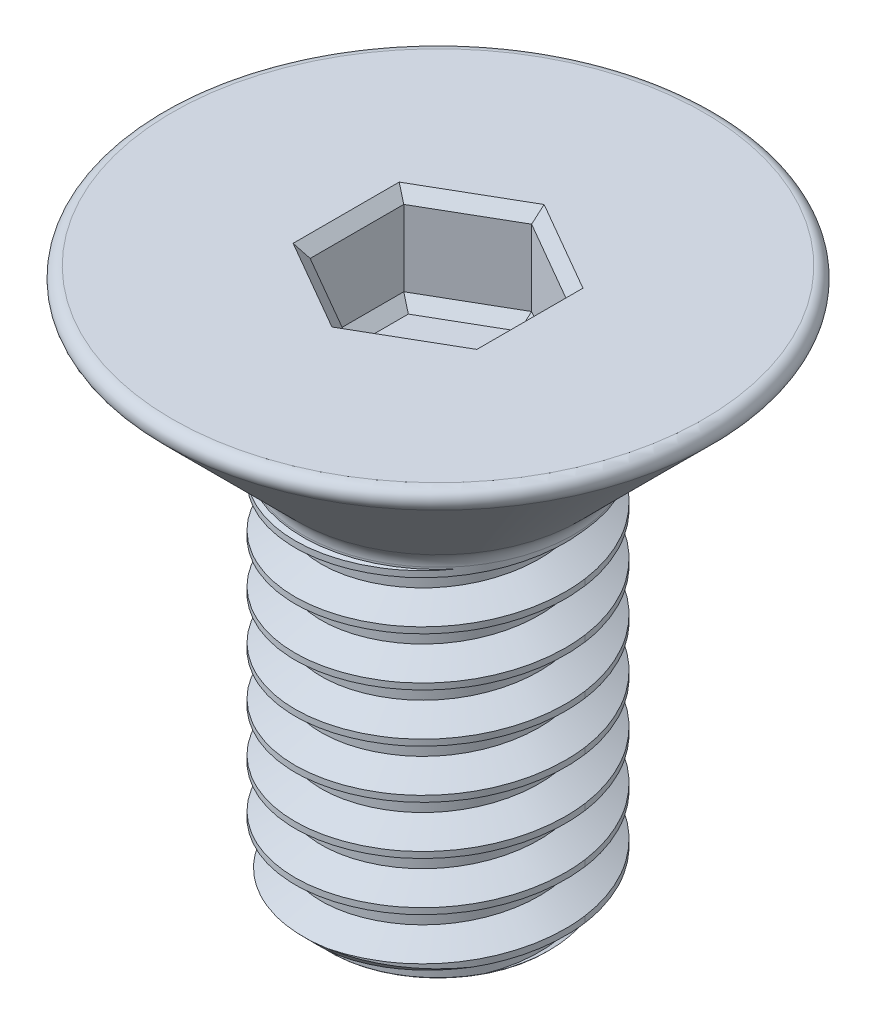
SolidWorks part; units mm, degrees
material "AISI Type A2 Tool Steel"
ref_plane "Front Plane" through (0, 0, 0) normal (0, 0, 1) x (1, 0, 0)
ref_plane "Top Plane" through (0, 0, 0) normal (0, 1, 0) x (1, 0, 0)
ref_plane "Right Plane" through (0, 0, 0) normal (1, 0, 0) x (0, 0, -1)
sketch "Sketch1" plane through (0, 0, 0) normal (0, 1, 0) x (1, 0, 0)
  circle A0 centre (0, 0) radius 1.25
  dimension "D1" = 2.5
extrude "Boss-Extrude1" add sketch "Sketch1" along normal blind 3.45
thread "Thread1" pitch 0.45 start angle 0, offset 1, length 0, pitch 0.45, diameter 2.5
ref_plane "Plane1" through (1.25, -1, 0) normal (0, 0, 1) x (1, 0, 0)
sketch "Thread Profile1" plane through (1.25, -1, 0) normal (0, 0, 1) x (1, 0, 0)
  line L0 (0, 0) -> (0, 0.45) construction
  line L11 (0, 0) -> (0, 0.3937)
  line L12 (0, 0.3937) -> (-0.2436, 0.2531)
  line L13 (-0.2436, 0.2531) -> (-0.2436, 0.1406)
  line L15 (-0.2436, 0.1406) -> (0, 0)
  line L17 (-0.2436, 0.1969) -> (0, 0.1969) construction
  point P2 (0, 0)
  dimension "Pitch" = 0.45
  dimension "Profile_Angle" = 60
  dimension "Profile_Land" = 0.1125
  dimension "Profile_Height" = 0.2436
sketch "Sketch5" plane through (0, 3.45, 0) normal (0, 1, 0) x (1, 0, 0)
  circle A0 centre (0, 0) radius 1.25
  dimension "D1" = 2.5
extrude "Boss-Extrude2" add sketch "Sketch5" along normal blind 0.1
sketch "Sketch6" plane through (0, 3.55, 0) normal (0, 1, 0) x (1, 0, 0)
  circle A0 centre (0, 0) radius 1.25
  dimension "D1" = 2.5
extrude "Boss-Extrude3" add sketch "Sketch6" along normal blind 1.45 draft 45 draft outward yes
fillet "Fillet1" radius 0.2 1 edges at (0, 3.55, 1.25)
fillet "Fillet2" radius 0.1 1 edges at (0, 5, 2.7)
sketch "Sketch7" plane through (0, 0, 0) normal (0, 0, 1) x (1, 0, 0)
  line L0 (0, 0) -> (0, 0.3237) construction
  line L1 (0, 0) -> (1.26, 0) construction
  line L2 (1.26, 0) -> (1.26, 0.26)
  line L3 (1.26, 0.26) -> (1, 0)
  line L4 (1, 0) -> (1.26, 0)
  dimension "D1" = 45
  dimension "D2" = 0.26
  dimension "D3" = 1.26
revolve "Cut-Revolve1" cut sketch "Sketch7" angle 360 about L0
sketch "Sketch8" plane through (0, 5, 0) normal (0, 1, 0) x (1, 0, 0)
  line L1 (0, 0.866) -> (-0.75, 0.433)
  line L2 (-0.75, 0.433) -> (-0.75, -0.433)
  line L3 (-0.75, -0.433) -> (0, -0.866)
  line L4 (0, -0.866) -> (0.75, -0.433)
  line L5 (0.75, -0.433) -> (0.75, 0.433)
  line L6 (0.75, 0.433) -> (0, 0.866)
  circle A0 centre (0, 0) radius 0.75 construction
  dimension "D1" = 1.5
extrude "Cut-Extrude1" cut sketch "Sketch8" against normal blind 0.8
chamfer "Chamfer1" distance 0.1 angle 45 6 edges at (-0.75, 5, 0) (-0.375, 5, 0.6495) (0.375, 5, 0.6495) (0.75, 5, 0) (0.375, 5, -0.6495) (-0.375, 5, -0.6495)
sketch "Sketch9" plane through (0, 4.2, 0) normal (0, 1, 0) x (1, 0, 0)
  line L1 (0, 0.866) -> (-0.75, 0.433)
  line L2 (-0.75, 0.433) -> (-0.75, -0.433)
  line L3 (-0.75, -0.433) -> (0, -0.866)
  line L4 (0, -0.866) -> (0.75, -0.433)
  line L5 (0.75, -0.433) -> (0.75, 0.433)
  line L6 (0.75, 0.433) -> (0, 0.866)
  circle A0 centre (0, 0) radius 0.75 construction
extrude "Cut-Extrude2" cut sketch "Sketch9" against normal blind 0.1 draft 45
